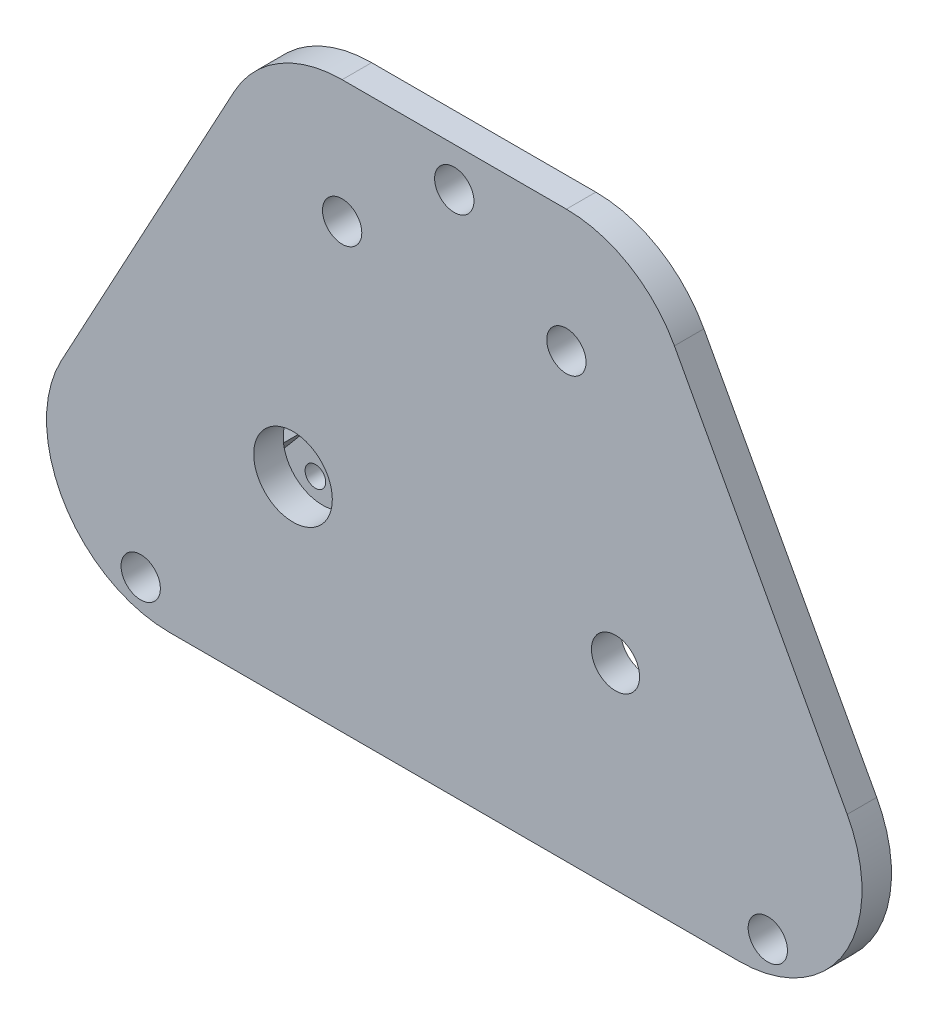
SolidWorks part; units mm, degrees
ref_plane "Front Plane" through (0, 0, 0) normal (0, 0, 1) x (1, 0, 0)
ref_plane "Top Plane" through (0, 0, 0) normal (0, 1, 0) x (1, 0, 0)
ref_plane "Right Plane" through (0, 0, 0) normal (1, 0, 0) x (0, 0, -1)
sketch "Sketch1" plane through (0, 0, 0) normal (0, 0, 1) x (1, 0, 0)
  line L0 (-11.41, 37.5) -> (11.41, 37.5)
  line L5 (-22.4037, 30.9487) -> (-39.9896, -1.5513)
  line L6 (-16.41, 0) -> (16.41, 0) construction
  line L7 (39.9896, -1.5513) -> (22.4037, 30.9487)
  line L8 (-28.9959, -20) -> (28.9959, -20)
  line L9 (0, 37.5) -> (0, -20) construction
  circle A0 centre (-16.41, 0) radius 16.41 construction
  circle A1 centre (16.41, 0) radius 16.41 construction
  circle A2 centre (-16.41, 0) radius 2.5
  circle A4 centre (-11.41, 25) radius 2
  circle A5 centre (11.41, 25) radius 2
  arc A7 (22.4037, 30.9487) -> (11.41, 37.5) centre (11.41, 25) ccw
  arc A8 (-34, 9.518) -> (-16.41, -20) centre (-16.41, 0) ccw
  arc A10 (16.41, -20) -> (34, 9.518) centre (16.41, 0) ccw
  arc A11 (-11.41, 37.5) -> (-22.4037, 30.9487) centre (-11.41, 25) ccw
  arc A12 (-39.9896, -1.5513) -> (-28.9959, -20) centre (-28.9959, -7.5) ccw
  arc A14 (39.9896, -1.5513) -> (28.9959, -20) centre (28.9959, -7.5) cw
  arc A15 (-10.2502, 37.5) -> (0, 17.5) centre (-24.6369, 17.5) cw
  arc A16 (0, 17.5) -> (10.2502, 37.5) centre (24.6369, 17.5) cw
  circle A17 centre (16.41, 0) radius 2.45
  circle A18 centre (0, 33.5) radius 2
  circle A19 centre (31.91, -16.6) radius 2
  circle A20 centre (-31.91, -16.6) radius 2
  circle A21 centre (-16.41, 0) radius 4
  point P19 (0, 37.5)
  dimension "D1" = 32.82
  dimension "D3" = 12.5
  dimension "D4" = 40
  dimension "D5" = 5
  dimension "D9" = 4
  dimension "D11" = 8
  dimension "D13" = 4.9
  dimension "D14" = 4
  dimension "D2" = 25
  dimension "D6" = 5
  dimension "D7" = 5
  dimension "D8" = 61.582
  dimension "D10" = 20
  dimension "D12" = 20
  dimension "D15" = 4
  dimension "D16" = 3.4
  dimension "D17" = 15.5
extrude "Boss-Extrude1" add sketch "Sketch1" along normal blind 3 contours A16 A15 L0 A11 L5 A8 L8 A10 L7 A7 A2 A21 A4 A5 | A15 A16 L0 A18 | A14 L7 A10 L8 A19 | L5 A12 L8 A8 A20 region at (0.1607, 5.8572, 0) region at (0, 37.2136, 0) region at (-35.2644, -10.5955, 0) region at (35.2644, -10.5955, 0)
sketch "Sketch2" plane through (0, 0, 0) normal (0, 0, -1) x (-1, 0, 0)
  line L0 (1.0607, 8.7249) -> (15.652, -8.6643)
  line L1 (1.0607, 8.7249) -> (10.483, 16.6312)
  line L2 (15.652, -8.6643) -> (25.0743, -0.758)
  line L3 (10.483, 16.6312) -> (25.0743, -0.758)
  line L4 (1.0607, 8.7249) -> (25.0743, -0.758) construction
  line L5 (15.652, -8.6643) -> (10.483, 16.6312) construction
  line L6 (23.5128, -8.4648) -> (2.6222, 16.4317) construction
  line L7 (25.8109, -6.5364) -> (4.9203, 18.36)
  line L8 (10.483, 16.6312) -> (7.3334, 20.3848)
  line L9 (7.3334, 20.3848) -> (-2.089, 12.4785)
  line L10 (-2.089, 12.4785) -> (1.0607, 8.7249)
  line L11 (15.652, -8.6643) -> (18.8016, -12.4179)
  line L12 (18.8016, -12.4179) -> (28.224, -4.5116)
  line L13 (28.224, -4.5116) -> (25.0743, -0.758)
  line L14 (28.9959, -20) -> (-28.9959, -20) construction
  line L15 (21.2147, -10.3932) -> (0.3241, 14.5033)
  circle A0 centre (16.41, 0) radius 4 construction
  circle A1 centre (4.0042, 14.7847) radius 1.05
  circle A2 centre (22.1308, -6.8178) radius 1.05
  point P1 (13.0675, 3.9834)
  point P2 (16.41, 0)
  point P19 (2.6222, 16.4317)
  point P23 (20.6455, -7.8275)
  dimension "D7" = 2.1
  dimension "D1" = 12.3
  dimension "D2" = 22.7
  dimension "D3" = 6.15
  dimension "D4" = 4.9
  dimension "D5" = 2.75
  dimension "D6" = 2.75
  dimension "D8" = 50
  dimension "D9" = 3
  dimension "D10" = 3
extrude "Boss-Extrude2" add sketch "Sketch2" along normal blind 8.3 contours L15 L1 L7 L9 A1 | L1 L15 L9 L10 | L8 L9 L7 L1 | L12 L15 L2 L11 | L15 L12 L7 L2 A2 | L12 L13 L2 L7 region at (-0.6924, 11.6141, 0) region at (-18.4333, -9.5287, 0) region at (-1.9821, 12.6963, 0) region at (-20.4329, -4.7944, 0) region at (-7.7017, 17.4956, 0) region at (-25.4426, -3.6472, 0)
extrude "Cut-Extrude1" cut sketch "Sketch2<3>" along normal blind 5 contours L15 L1 L7 L9 A1 | L15 L12 L7 L2 A2 region at (-1.9821, 12.6963, 0) region at (-20.4329, -4.7944, 0)
sketch "Sketch2<3>" plane through (0, 0, 0) normal (0, 0, -1) x (-1, 0, 0) same geometry as "Sketch2"
sketch "Sketch3" plane through (0, 0, 0) normal (1, 0, 0) x (0, 0, -1)
  line L1 (-0.0432, -5.1254) -> (9.6064, -5.1254)
  line L2 (-0.0432, -5.1254) -> (-0.0432, -33.2501)
  line L3 (-0.0432, -33.2501) -> (9.6064, -33.2501)
  line L4 (9.6064, -5.1254) -> (9.6064, -33.2501)
  line L5 (-0.0432, -5.1254) -> (9.6064, -33.2501) construction
  line L6 (-0.0432, -33.2501) -> (9.6064, -5.1254) construction
  point P0 (4.7816, -19.1878)
  point P5 (2.5, -19.1878)
extrude "Boss-Extrude3" [suppressed] add sketch "Sketch3" against normal blind 5 from offset 8.9154 offset against normal yes
